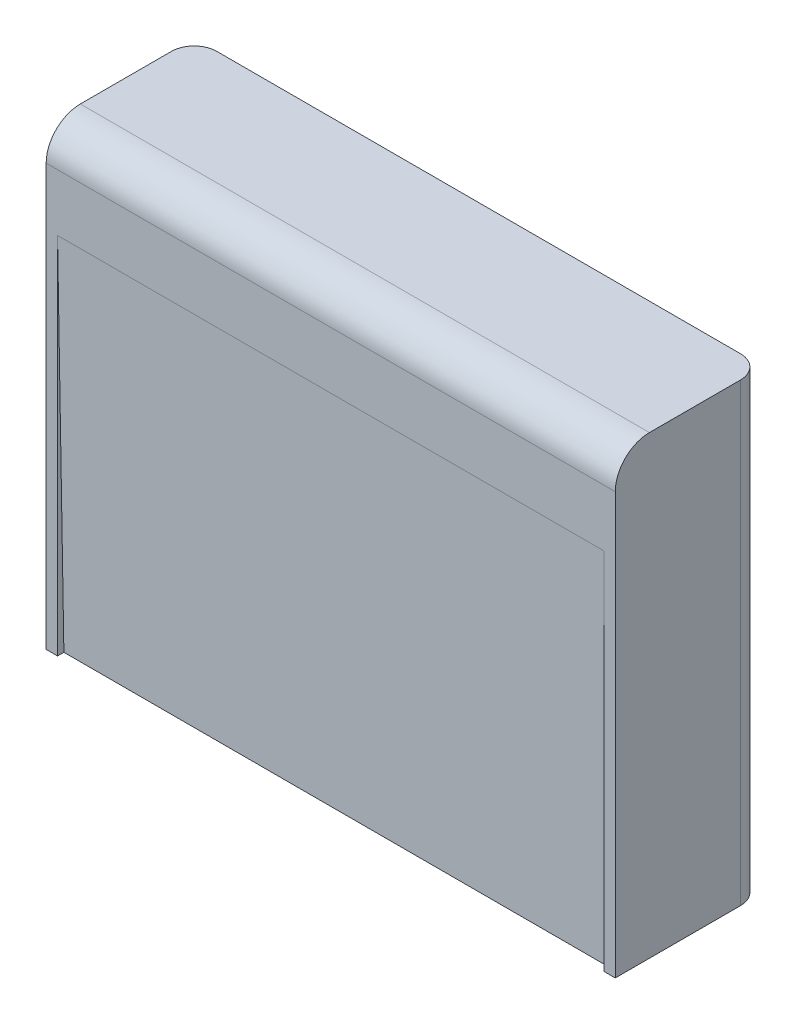
SolidWorks part; units mm, degrees
material "K110"
ref_plane "Front Plane" through (0, 0, 0) normal (0, 0, 1) x (1, 0, 0)
ref_plane "Top Plane" through (0, 0, 0) normal (0, 1, 0) x (1, 0, 0)
ref_plane "Right Plane" through (0, 0, 0) normal (1, 0, 0) x (0, 0, -1)
sketch "Sketch1" plane through (0, 0, 0) normal (0, 1, 0) x (1, 0, 0)
  line L1 (-25, -6.5) -> (25, -6.5)
  line L2 (-25, -6.5) -> (-25, 6.5)
  line L3 (-25, 6.5) -> (25, 6.5)
  line L4 (25, -6.5) -> (25, 6.5)
  line L5 (-25, -6.5) -> (25, 6.5) construction
  line L6 (-25, 6.5) -> (25, -6.5) construction
  point P0 (0, 0)
  dimension "D1" = 13
  dimension "D2" = 50
extrude "Boss-Extrude1" add sketch "Sketch1" against normal blind 40
fillet "Fillet1" radius 2 2 edges at (-25, -20, -6.5) (25, -20, -6.5)
fillet "Fillet2" radius 3 1 edges at (0, 0, 6.5) tangent propagation no
hole_wizard "M6 Tapped Hole1" positions "Sketch4" profile "Sketch3" tap size "M6" standard "ISO"
sketch "Sketch4" plane through (0, -40, 0) normal (0, -1, 0) x (-1, 0, 0)
  line L0 (-25, -6.5) -> (-25, 4.5) construction
  line L1 (25, 4.5) -> (25, -6.5) construction
  point P0 (-17.5, 0)
  point P2 (17.5, 0)
  dimension "D1" = 7.5
  dimension "D2" = 7.5
sketch "Sketch3" plane through (17.5, -40, 0) normal (1, 0, 0) x (0, 0, -1)
  line L0 (0, 0) -> (0, 18.5022)
  line L1 (0, 18.5022) -> (2.5, 17)
  line L2 (2.5, 17) -> (2.5, 0.525)
  line L3 (2.5, 0.525) -> (3.025, 0)
  line L5 (3.025, 0) -> (0, 0)
  line L6 (-2.5, 0.525) -> (-3.025, 0) construction
  line L10 (0, 18.5022) -> (-2.5, 17) construction
  line L11 (0, -6.35) -> (0, 107.95) construction
  dimension "Tap Drill Dia." = 5
  dimension "Tap Drill Depth" = 17
  dimension "Near C'Sink Dia." = 6.05
  dimension "Near C'Sink Angle" = 90
  dimension "Drill Angle" = 118
cosmetic thread "Hole Thread1" parameters "D1"=12, "D2"=6
cosmetic thread "Hole Thread2" parameters "D1"=12, "D2"=6
sketch "Sketch5" plane through (0, 0, 0) normal (1, 0, 0) x (0, 0, -1)
  line L4 (-6.5, -8) -> (-5.9414, -40)
  line L5 (-6.5, -40) -> (-6.5, -3) construction
  line L6 (-6.5, -40) -> (-4.5, -40) construction
  line L7 (-5.9414, -40) -> (-6.5, -40)
  line L8 (-6.5, -40) -> (-6.5, -8)
  dimension "D1" = 5
  dimension "D2" = 1
extrude "Cut-Extrude1" cut sketch "Sketch5" against normal mid plane 48
